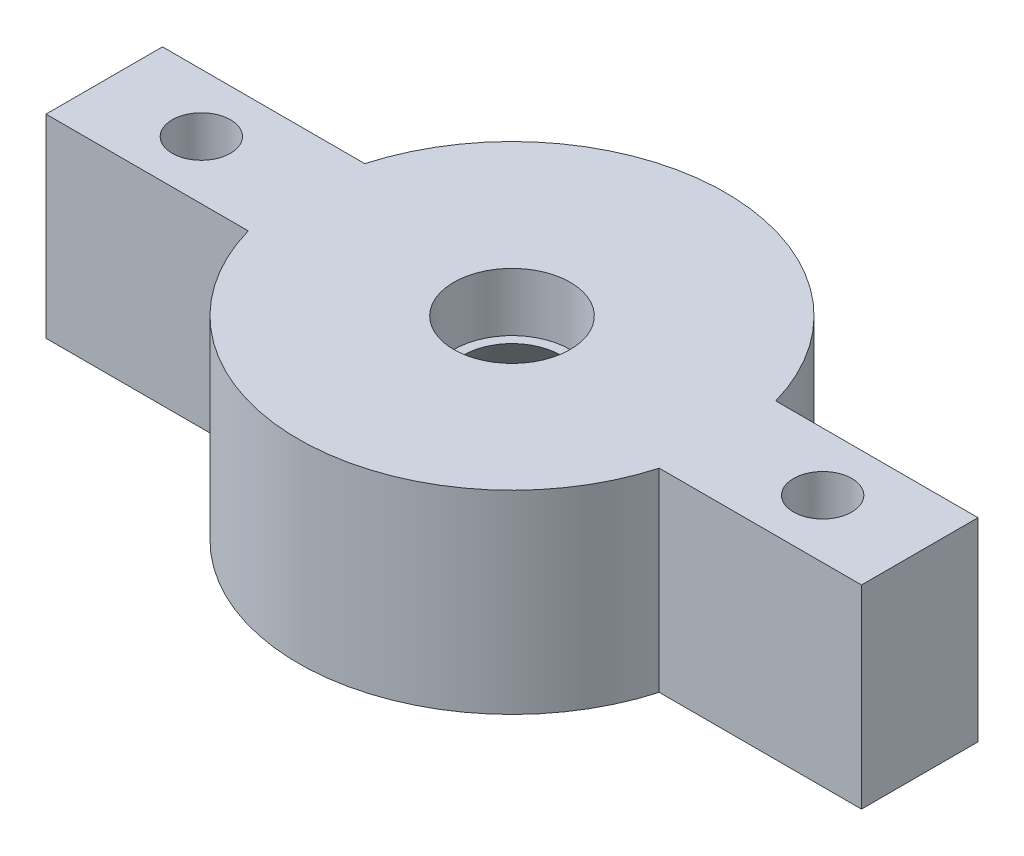
SolidWorks part; units mm, degrees
ref_plane "Front Plane" through (0, 0, 0) normal (0, 0, 1) x (1, 0, 0)
ref_plane "Top Plane" through (0, 0, 0) normal (0, 1, 0) x (1, 0, 0)
ref_plane "Right Plane" through (0, 0, 0) normal (1, 0, 0) x (0, 0, -1)
sketch "Sketch2" plane through (0, 0, 0) normal (1, 0, 0) x (0, 0, -1)
  line L1 (-3, -5) -> (3, -5)
  line L2 (-3, -5) -> (-3, 5)
  line L3 (-3, 5) -> (3, 5)
  line L4 (3, -5) -> (3, 5)
  line L5 (-3, -5) -> (3, 5) construction
  line L6 (-3, 5) -> (3, -5) construction
  point P0 (0, 0)
  dimension "D1" = 6
  dimension "D2" = 10
extrude "Boss-Extrude1" add sketch "Sketch2" along normal blind 42
sketch "Sketch3" plane through (0, 5, 0) normal (0, 1, 0) x (1, 0, 0)
  line L0 (0, 0) -> (42, 0) construction
  line L1 (42, 3) -> (42, -3) construction
  circle A0 centre (21, 0) radius 11
  dimension "D1" = 22
extrude "Boss-Extrude2" add sketch "Sketch3" against normal up to surface (10 mm away) up to face at (21, -5, 0)
sketch "Sketch4" plane through (0, -5, 0) normal (0, -1, 0) x (-1, 0, 0)
  circle A0 centre (-21, 0) radius 7.5
  circle A1 centre (-21, 0) radius 11 construction
  dimension "D1" = 15
extrude "Cut-Extrude1" cut sketch "Sketch4" against normal blind 2
sketch "Sketch5" plane through (0, 0, 0) normal (0, 0, -1) x (-1, 0, 0)
  line L0 (-21, -3) -> (-28.5, -3)
  line L2 (-28.5, -3) -> (-23.5, 2)
  line L3 (-23.5, 2) -> (-21, 2)
  line L5 (-21, 2) -> (-21, -3)
  line L6 (-31.583, -5) -> (-10.417, -5) construction
  line L7 (-10.417, 5) -> (-31.583, 5) construction
  point P10 (-21, 5)
  dimension "D1" = 2
  dimension "D2" = 7.5
  dimension "D3" = 2.5
  dimension "D4" = 5
revolve "Cut-Revolve1" cut sketch "Sketch5" angle 360 about L5
sketch "Sketch6" plane through (0, 2, 0) normal (0, -1, 0) x (1, 0, 0)
  circle A0 centre (21, 0) radius 3
  circle A1 centre (21, 0) radius 2.5
  circle A2 centre (21, 0) radius 2.5 construction
  dimension "D2" = 0.5
  dimension "D1" = 0
extrude "Cut-Extrude2" cut sketch "Sketch6" against normal blind 13
fillet "Fillet1" radius 2 1 edges at (21, -5, -7.5)
sketch "Sketch7" plane through (0, -5, 0) normal (0, -1, 0) x (1, 0, 0)
  line L0 (0, 3) -> (0, -3) construction
  line L1 (21, 11) -> (21, -11) construction
  circle A0 centre (5, 0) radius 1.5
  arc A1 (31.583, 3) -> (10.417, 3) centre (21, 0) ccw construction
  arc A2 (10.417, -3) -> (31.583, -3) centre (21, 0) ccw construction
  circle A3 centre (37, 0) radius 1.5
  dimension "D1" = 3
  dimension "D2" = 5
extrude "Cut-Extrude3" cut sketch "Sketch7" against normal up to next
